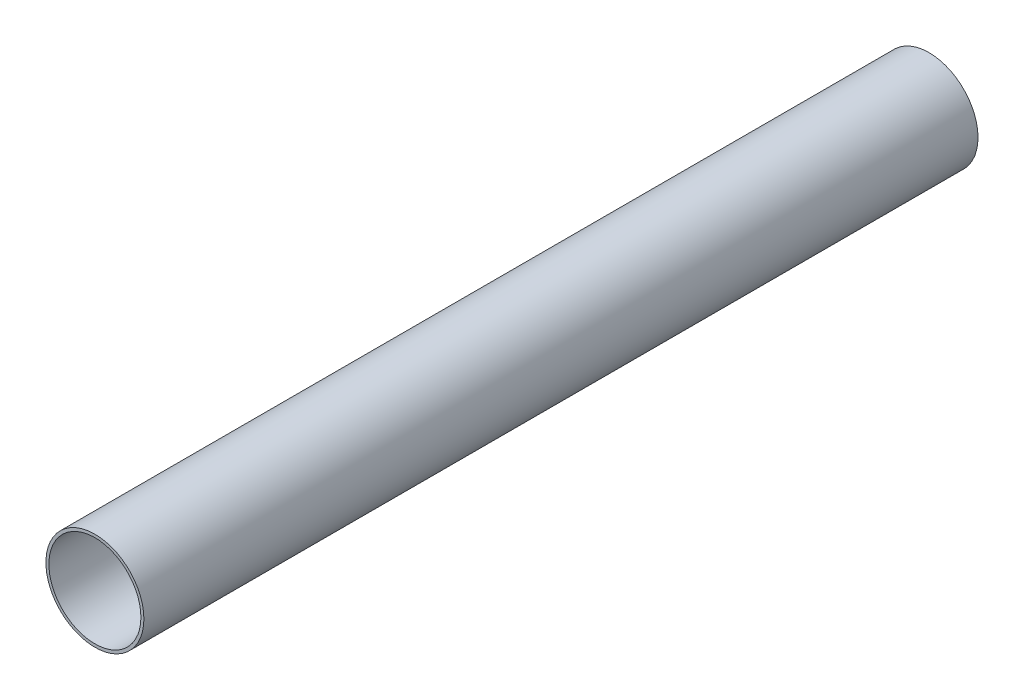
SolidWorks part; units mm, degrees
ref_plane "Front Plane" through (0, 0, 0) normal (0, 0, 1) x (1, 0, 0)
ref_plane "Top Plane" through (0, 0, 0) normal (0, 1, 0) x (1, 0, 0)
ref_plane "Right Plane" through (0, 0, 0) normal (1, 0, 0) x (0, 0, -1)
sketch "Sketch1" plane through (0, 0, 0) normal (0, 0, 1) x (1, 0, 0)
  circle A0 centre (0, 0) radius 20.555
  dimension "D1" = 41.11
extrude "Boss-Extrude3" add sketch "Sketch1" against normal blind 350
sketch "Sketch4" plane through (0, 0, 0) normal (0, 0, 1) x (1, 0, 0)
  circle A0 centre (0, 0) radius 19.305
  dimension "D1" = 38.61
extrude "Cut-Extrude2" cut sketch "Sketch4" against normal up to next
